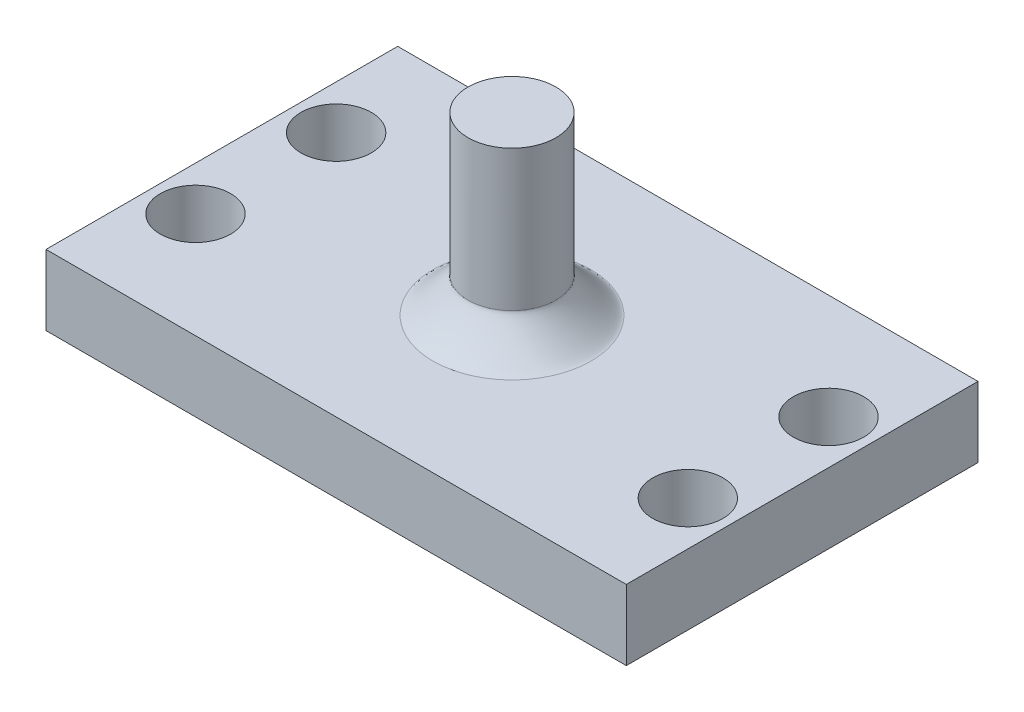
SolidWorks part; units mm, degrees
ref_plane "Front Plane" through (0, 0, 0) normal (0, 0, 1) x (1, 0, 0)
ref_plane "Top Plane" through (0, 0, 0) normal (0, 1, 0) x (1, 0, 0)
ref_plane "Right Plane" through (0, 0, 0) normal (1, 0, 0) x (0, 0, -1)
sketch "Sketch1" plane through (0, 0, 0) normal (0, 1, 0) x (1, 0, 0)
  line L1 (16.5, -10) -> (-16.5, -10)
  line L2 (16.5, -10) -> (16.5, 10)
  line L3 (16.5, 10) -> (-16.5, 10)
  line L4 (-16.5, -10) -> (-16.5, 10)
  line L5 (16.5, -10) -> (-16.5, 10) construction
  line L6 (16.5, 10) -> (-16.5, -10) construction
  point P0 (0, 0)
  dimension "D1" = 33
  dimension "D2" = 20
extrude "Boss-Extrude1" add sketch "Sketch1" along normal mid plane 4
sketch "Sketch2" plane through (0, 2, 0) normal (0, 1, 0) x (1, 0, 0)
  line L0 (-14, 4) -> (-14, -4) construction
  line L1 (-14, 0) -> (0, 0) construction
  line L2 (0, 0) -> (0, -10) construction
  line L3 (-16.5, -10) -> (16.5, -10) construction
  circle A0 centre (-14, 4) radius 2
  circle A1 centre (-14, -4) radius 2
  circle A4 centre (14, -4) radius 2
  circle A5 centre (14, 4) radius 2
  dimension "D1" = 4
  dimension "D2" = 14
  dimension "D3" = 8
extrude "Cut-Extrude1" cut sketch "Sketch2" against normal through all
sketch "Sketch3" plane through (0, 2, 0) normal (0, 1, 0) x (1, 0, 0)
  circle A0 centre (0, 0) radius 2.5
  dimension "D1" = 5
extrude "Boss-Extrude2" add sketch "Sketch3" along normal blind 10
fillet "Fillet1" radius 2 1 edges at (0, 2, 2.5) conic radius 10
